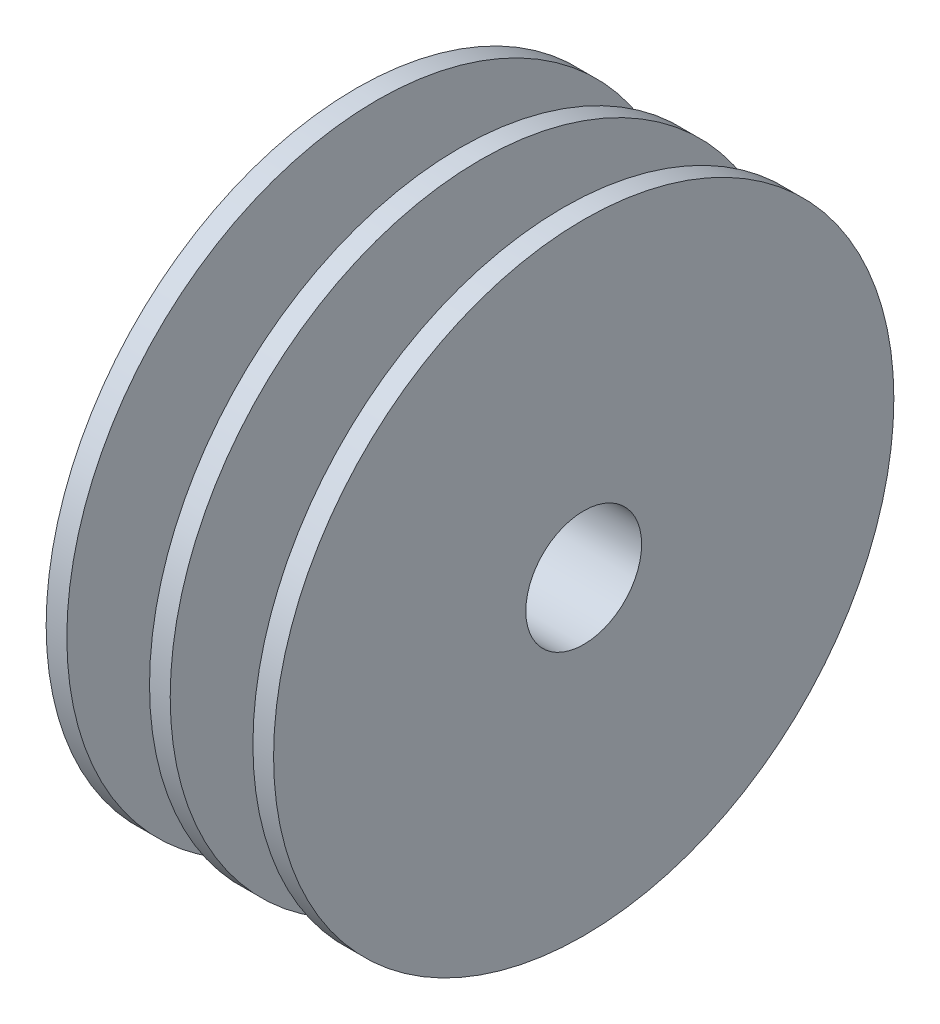
SolidWorks part; units mm, degrees
ref_plane "Front Plane" through (0, 0, 0) normal (0, 0, 1) x (1, 0, 0)
ref_plane "Top Plane" through (0, 0, 0) normal (0, 1, 0) x (1, 0, 0)
ref_plane "Right Plane" through (0, 0, 0) normal (1, 0, 0) x (0, 0, -1)
sketch "Sketch2" plane through (0, 0, 0) normal (1, 0, 0) x (0, 0, -1)
  circle A0 centre (0, 0) radius 15
  circle A1 centre (0, 0) radius 5
  dimension "D1" = 30
  dimension "D2" = 10
extrude "Boss-Extrude1" add sketch "Sketch2" along normal blind 1 contours A0 A1 | A1 region at (0, 0, 14.5757) region at (0, 0, 0)
extrude "Boss-Extrude2" add sketch "Sketch2<3>" along normal blind 4 from surface contours A1 region at (0, 0, 0) starting at face at (1, 0, -15)
sketch "Sketch2<3>" plane through (0, 0, 0) normal (1, 0, 0) x (0, 0, -1) same geometry as "Sketch2"
extrude "Boss-Extrude3" add sketch "Sketch2<5>" along normal blind 1 from surface contours A0 A1 | A1 region at (0, 0, 14.5757) region at (0, 0, 0) starting at face at (5, 0, -5)
sketch "Sketch2<5>" plane through (0, 0, 0) normal (1, 0, 0) x (0, 0, -1) same geometry as "Sketch2"
extrude "Boss-Extrude4" add sketch "Sketch2<6>" along normal blind 4 from surface contours A1 region at (0, 0, 0) starting at face at (6, 0, -15)
sketch "Sketch2<6>" plane through (0, 0, 0) normal (1, 0, 0) x (0, 0, -1) same geometry as "Sketch2"
extrude "Boss-Extrude5" add sketch "Sketch2<7>" along normal blind 1 from surface contours A1 | A0 A1 region at (0, 0, 14.5757) region at (0, 0, 0) starting at face at (10, 0, -5)
sketch "Sketch2<7>" plane through (0, 0, 0) normal (1, 0, 0) x (0, 0, -1) same geometry as "Sketch2"
sketch "Sketch3" plane through (0, 0, 0) normal (-1, 0, 0) x (0, 0, 1)
  circle A1 centre (0, 0) radius 2.375
  circle A2 centre (0, 0) radius 0.6
  circle A3 centre (0, 0) radius 2.8
  point P5 (0, 2.375)
  dimension "D1" = 4.75
  dimension "D3" = 1.2
  dimension "D4" = 5.6
extrude "Cut-Extrude1" cut sketch "Sketch3" against normal blind 2 contours A2 A1 | A2 region at (0, 0, -2.3078) region at (0, 0, 0)
extrude "Cut-Extrude6" cut sketch "Sketch3<4>" against normal up to surface (11 mm away) from offset 3 contours A1 | A2 A1 | A2 | A3 A1 region at (0, 0, -2.3078) region at (0, 0, 0) region at (0, 0, -2.7208) up to face at (11, 0, -15) offset against normal yes
sketch "Sketch3<4>" plane through (0, 0, 0) normal (-1, 0, 0) x (0, 0, 1) same geometry as "Sketch3"
extrude "Cut-Extrude7" cut sketch "Sketch3<5>" against normal up to surface (3 mm away) contours A2 region at (0, 0, 0) up to face at (3, 0, 2.8)
sketch "Sketch3<5>" plane through (0, 0, 0) normal (-1, 0, 0) x (0, 0, 1) same geometry as "Sketch3"
equation "\"e\"=4"
